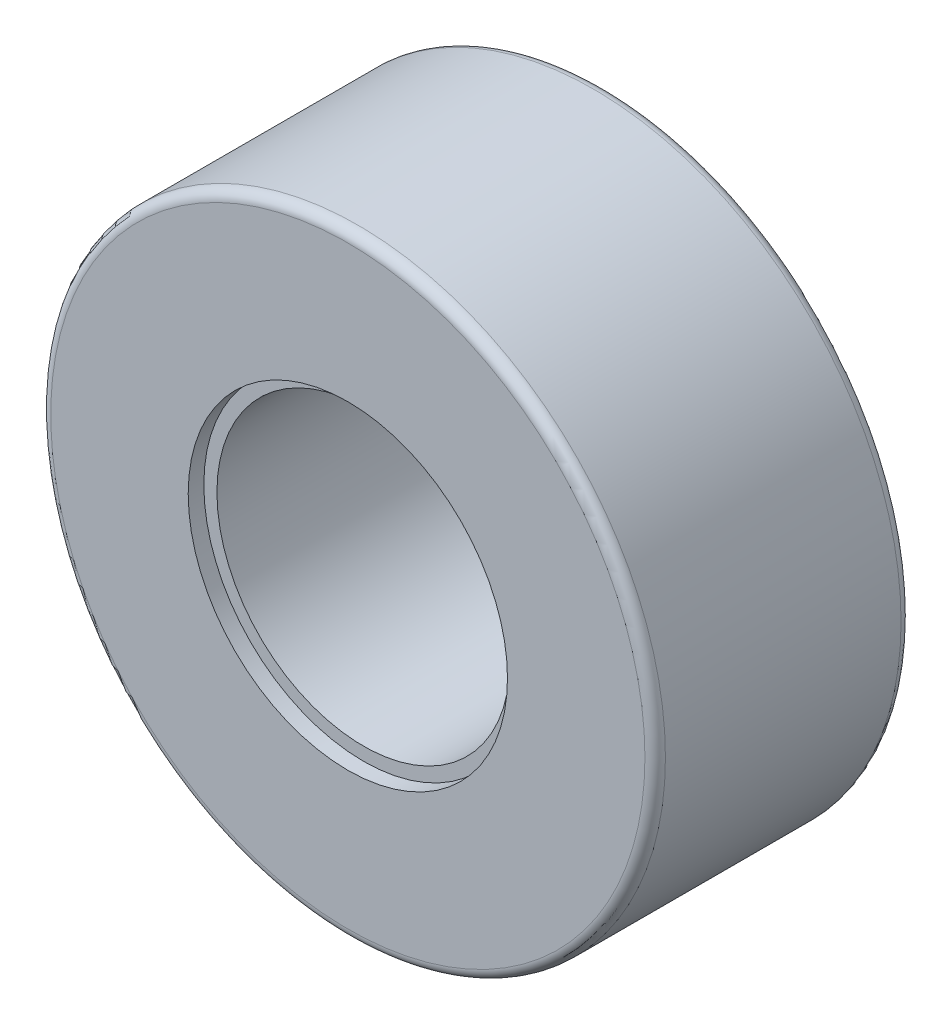
SolidWorks part; units mm, degrees
material "PETG"
ref_plane "Front Plane" through (0, 0, 0) normal (0, 0, 1) x (1, 0, 0)
ref_plane "Top Plane" through (0, 0, 0) normal (0, 1, 0) x (1, 0, 0)
ref_plane "Right Plane" through (0, 0, 0) normal (1, 0, 0) x (0, 0, -1)
sketch "Sketch1" plane through (0, 0, 0) normal (0, 0, 1) x (1, 0, 0)
  circle A0 centre (0, 0) radius 14.3025
  circle A1 centre (0, 0) radius 30
  dimension "D1" = 60
  dimension "D2" = 28.605
extrude "Boss-Extrude1" add sketch "Sketch1" along normal mid plane 25
sketch "Sketch3" plane through (0, 0, 12.5) normal (0, 0, 1) x (1, 0, 0)
  circle A0 centre (0, 0) radius 15.5825
  dimension "D1" = 31.165
extrude "Cut-Extrude1" cut sketch "Sketch3" against normal blind 1.524
mirror "Mirror1" about plane through (0, 0, 0) normal (0, 0, 1) of "Cut-Extrude1"
sketch "Sketch4" plane through (0, 0, 0) normal (0, 1, 0) x (1, 0, 0)
  line L0 (30, -12.5) -> (30, 12.5) construction
  line L2 (30, -12.5) -> (30, 12.5)
  line L3 (0, 0) -> (0, 50000) construction
  arc A0 (30, -12.5) -> (30, 12.5) centre (-18.4123, 0) ccw
  point P10 (31.5877, 0)
  dimension "D1" = 50
fillet "Fillet1" radius 1 2 edges at (30, 0, -12.5) (30, 0, 12.5)
revolve "Revolve1" [suppressed] add sketch "Sketch4" angle 360 about L3
equation "\"tol_dia_id_intfc\" = 0.0200mm ' For hole diameters - Interference fit"
equation "\"tol_dia_id_slip\"  = 0.0300mm ' For hole diameters - Slip fit"
equation "\"tol_dia_id_clear\" = 0.0500mm ' For hole diameters - Clearance fit"
equation "\"tol_dia_od_intfc\" = 0.0200mm ' For shaft diameters - Interference fit"
equation "\"tol_dia_od_slip\"  = 0.0300mm ' For shaft diameters - Slip fit"
equation "\"tol_dia_od_clear\" = 0.0500mm ' For shaft diameters - Clearance fit"
equation "\"tol_general_intfc\"= 0.0030mm ' For general parts (Horiz) - Interference fit"
equation "\"tol_general_slip\" = 0.0050mm ' For general parts (Horiz) - Slip fit"
equation "\"tol_general_clear\"= 0.0100mm ' For general parts (Horiz) - Clearance fit"
equation "\"tol_layer_intfc\"  = 0.0030mm ' For all parts (Vert) - Interference fit"
equation "\"tol_layer_slip\"   = 0.0050mm ' For all parts (Vert) - Slip fit"
equation "\"tol_layer_clear\"  = 0.0100mm ' For all parts (Vert) - Clearance fit"
equation "\"tol_corner_rad\"   = 0.100mm ' For corners that fit into other parts"
equation "\"D2@Sketch1\"=1.125in + \"tol_dia_id_slip\""
equation "\"D1@Sketch3\"=1.225in + \"tol_dia_id_clear\""
